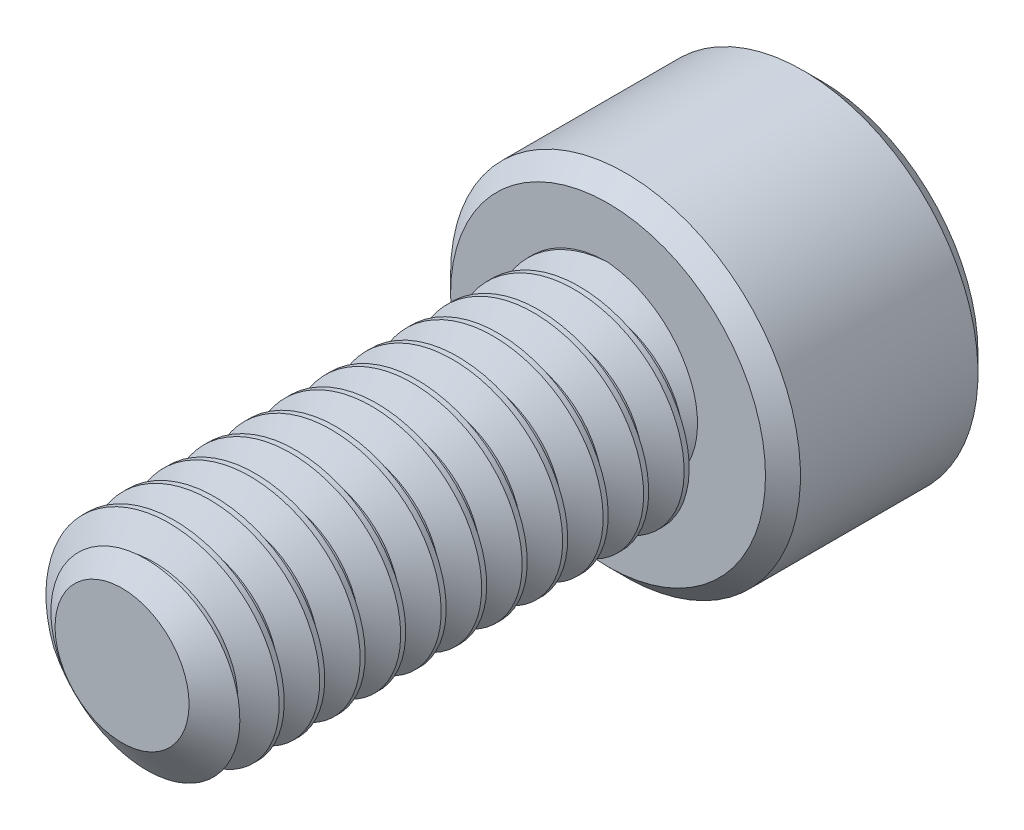
SolidWorks part; units mm, degrees
other "DetailItem1"
ref_plane "Front Plane" through (0, 0, 0) normal (0, 0, 1) x (1, 0, 0)
ref_plane "Top Plane" through (0, 0, 0) normal (0, 1, 0) x (1, 0, 0)
ref_plane "Right Plane" through (0, 0, 0) normal (1, 0, 0) x (0, 0, -1)
sketch "Sketch1" plane through (0, 0, 0) normal (0, 0, 1) x (1, 0, 0)
  circle A0 centre (0, 0) radius 2.0828
  dimension "OD" = 4.1656
extrude "Extrude1" add sketch "Sketch1" against normal blind 9.525
sketch "Sketch2" plane through (0, 0, 0) normal (0, 0, 1) x (1, 0, 0)
  circle A0 centre (0, 0) radius 2.0828 construction
  circle A1 centre (0, 0) radius 2.0828
curve "Helix/Spiral1" pitch 0.7937 height 10.3188 turns 13 parameters "pitch"=0.7937
sketch "Sketch3" plane through (0, 0, 0) normal (1, 0, 0) x (0, 0, -1)
  line L0 (-0.6945, 2.0828) -> (-0.3969, 1.5672)
  line L1 (-0.3969, 1.5672) -> (-0.2977, 1.5672)
  line L2 (-0.2977, 1.5672) -> (0, 2.0828)
  line L3 (-0.6945, 2.0828) -> (0, 2.0828)
  line L4 (-0.3473, 2.0828) -> (-0.3473, 1.5672) construction
  line L5 (-0.5457, 1.825) -> (-0.1488, 1.825) construction
  line L6 (0, 2.0828) -> (0, -2.0828) construction
  dimension "D1" = 0.0992
  dimension "D2" = 0.3969
  dimension "D3" = 60
sweep "Cut-Sweep1" cut profiles "Sketch3" path "Helix/Spiral1"
sketch "Sketch4" plane through (0, 0, 0) normal (1, 0, 0) x (0, 0, -1)
  line L0 (0.5388, 2.0828) -> (0, 1.3132)
  line L1 (0, 1.3132) -> (0, 2.0828)
  line L2 (0.5388, 2.0828) -> (0, 2.0828)
  line L3 (-0.6945, 2.0828) -> (0, 2.0828) construction
  line L4 (0, 0) -> (7.0209, 0) construction
  dimension "D1" = 55
  dimension "D2" = 0.254
revolve "Cut-Revolve1" cut sketch "Sketch4" angle 360 about L4
sketch "Sketch5" plane through (0, 0, 0) normal (1, 0, 0) x (0, 0, -1)
  line L0 (9.525, -1.5805) -> (9.525, 1.4861) construction
  line L1 (9.525, 2.2098) -> (0.1202, 2.2098)
  line L2 (9.525, 2.2098) -> (9.525, 0)
  line L3 (9.525, 0) -> (0, 0)
  line L4 (0, 1.8796) -> (0, 0)
  line L5 (0.1202, 2.2098) -> (0, 1.8796)
  line L6 (0, 0) -> (9.9695, 0) construction
  point P3 (0, 2.2098)
  point P10 (0, 2.2098)
  dimension "D1" = 0.3302
  dimension "D2" = 0.127
  dimension "D3" = 20
  dimension "Min Thread" = 0
revolve "partially thread" [suppressed] add sketch "Sketch5" angle 360 about L6
sketch "Sketch6" plane through (0, 0, -9.525) normal (0, 0, -1) x (-1, 0, 0)
  circle A0 centre (0, 0) radius 3.429
  dimension "head dia" = 6.858
extrude "Extrude2" add sketch "Sketch6" along normal blind 4.1656
sketch "Sketch7" plane through (0, 0, -13.6906) normal (0, 0, -1) x (-1, 0, 0)
  line L1 (0, 2.0622) -> (-1.7859, 1.0311)
  line L2 (-1.7859, 1.0311) -> (-1.7859, -1.0311)
  line L3 (-1.7859, -1.0311) -> (0, -2.0622)
  line L4 (0, -2.0622) -> (1.7859, -1.0311)
  line L5 (1.7859, -1.0311) -> (1.7859, 1.0311)
  line L6 (1.7859, 1.0311) -> (0, 2.0622)
  circle A0 centre (0, 0) radius 1.7859 construction
  dimension "hex dia" = 3.5719
extrude "Cut-Extrude1" cut sketch "Sketch7" against normal blind 2.6789
sketch "Sketch8" plane through (0, 0, -13.6906) normal (0, 0, -1) x (-1, 0, 0)
  circle A0 centre (0, 0) radius 2.0622
extrude "Cut-Extrude2" cut sketch "Sketch8" against normal through all draft 45
chamfer "Chamfer1" distance 0.3429 angle 45 2 edges at (-3.429, 0, -13.6906) (-3.429, 0, -9.525)
sketch "Sketch9" plane through (0, 0, 0) normal (1, 0, 0) x (0, 0, -1)
  line L0 (0, 2.0828) -> (0, -2.0828) construction
  line L1 (1.9844, 2.0828) -> (1.9844, -2.0828) construction
  dimension "D1" = 1.9844
equation "\"D3@Helix/Spiral1\" = \"screw length@Extrude1\"+\"pitch@Helix/Spiral1\""
equation "\"D1@Sketch3\" = \"pitch@Helix/Spiral1\"*.125"
equation "\"D2@Sketch3\" = \"pitch@Helix/Spiral1\"*.5"
equation "\"D1@Cut-Extrude1\" = \"hex dia@Sketch7\"*.75"
equation "\"D1@Chamfer1\" = \"head dia@Sketch6\"*.05"
equation "\"D1@Sketch9\" = \"pitch@Helix/Spiral1\"*2.5"
